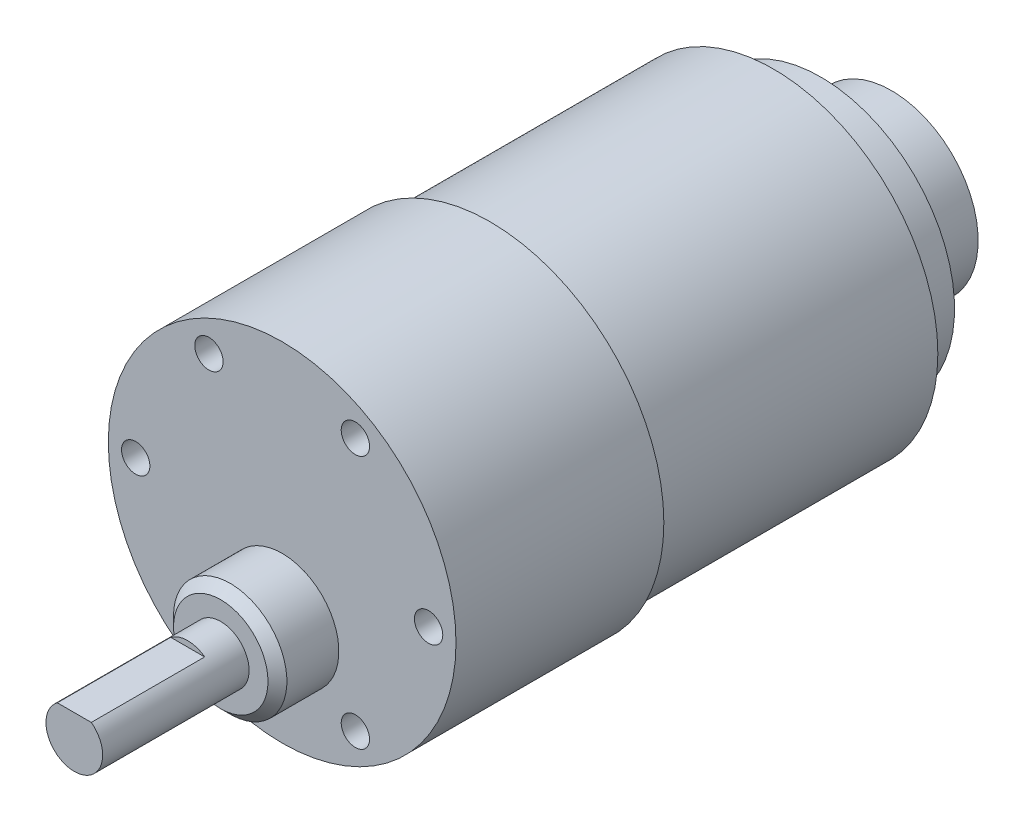
SolidWorks part; units mm, degrees
material "1060 Alloy"
ref_plane "Front Plane" through (0, 0, 0) normal (0, 0, 1) x (1, 0, 0)
ref_plane "Top Plane" through (0, 0, 0) normal (0, 1, 0) x (1, 0, 0)
ref_plane "Right Plane" through (0, 0, 0) normal (1, 0, 0) x (0, 0, -1)
sketch "Sketch1" plane through (0, 0, 0) normal (0, 0, 1) x (1, 0, 0)
  circle A0 centre (0, 0) radius 18.4
  dimension "D1" = 36.8
extrude "Boss-Extrude1" add sketch "Sketch1" along normal blind 22
sketch "Sketch2" plane through (0, 0, 0) normal (0, 0, -1) x (-1, 0, 0)
  circle A2 centre (0, 0) radius 17.4
  circle A3 centre (0, 0) radius 17.4
  dimension "D1" = 1
extrude "Boss-Extrude2" add sketch "Sketch2" along normal blind 30
sketch "Sketch3" plane through (0, 0, 22) normal (0, 0, 1) x (1, 0, 0)
  circle A0 centre (0, -7) radius 6
  dimension "D2" = 12
  dimension "D1" = 7
extrude "Boss-Extrude3" add sketch "Sketch3" along normal blind 6.5
chamfer "Chamfer1" distance 1 angle 45 1 edges at (6, -7, 28.5)
sketch "Sketch4" plane through (0, 0, 28.5) normal (0, 0, 1) x (1, 0, 0)
  circle A0 centre (0, -7) radius 3
  dimension "D1" = 6
extrude "Boss-Extrude4" add sketch "Sketch4" along normal blind 15.5
sketch "Sketch5" plane through (0, 0, 0) normal (1, 0, 0) x (0, 0, -1)
  line L0 (-44, -10) -> (-28.5, -10) construction
  line L1 (-44, -4) -> (-32, -4)
  line L2 (-44, -4) -> (-44, -4.6)
  line L3 (-44, -4.6) -> (-32, -4.6)
  line L4 (-32, -4) -> (-32, -4.6)
  dimension "D1" = 12
  dimension "D2" = 5.4
extrude "Cut-Extrude1" cut sketch "Sketch5" against normal blind 15.5 and the other way blind 15.5
sketch "Sketch6" plane through (0, 0, 22) normal (0, 0, 1) x (1, 0, 0)
  circle A0 centre (0, 0) radius 15.5 construction
  circle A1 centre (-7.75, 13.4234) radius 1.5
  circle A2 centre (7.75, 13.4234) radius 1.5
  circle A3 centre (15.5, 0) radius 1.5
  circle A4 centre (-15.5, 0) radius 1.5
  circle A5 centre (-7.75, -13.4234) radius 1.5
  circle A6 centre (7.75, -13.4234) radius 1.5
  dimension "D1" = 31
  dimension "D2" = 3
  dimension "D3" = 15.5
extrude "Cut-Extrude2" cut sketch "Sketch6" against normal blind 5
sketch "Sketch7" plane through (0, 0, -30) normal (0, 0, -1) x (-1, 0, 0)
  circle A0 centre (0, 0) radius 9.1683
extrude "Boss-Extrude5" add sketch "Sketch7" along normal blind 12.5
sketch "Sketch8" plane through (0, 0, -30) normal (0, 0, -1) x (-1, 0, 0)
  circle A2 centre (0, 0) radius 14.1683
  circle A3 centre (0, 0) radius 14.1683
  dimension "D1" = 5
extrude "Boss-Extrude6" add sketch "Sketch8" along normal blind 5
